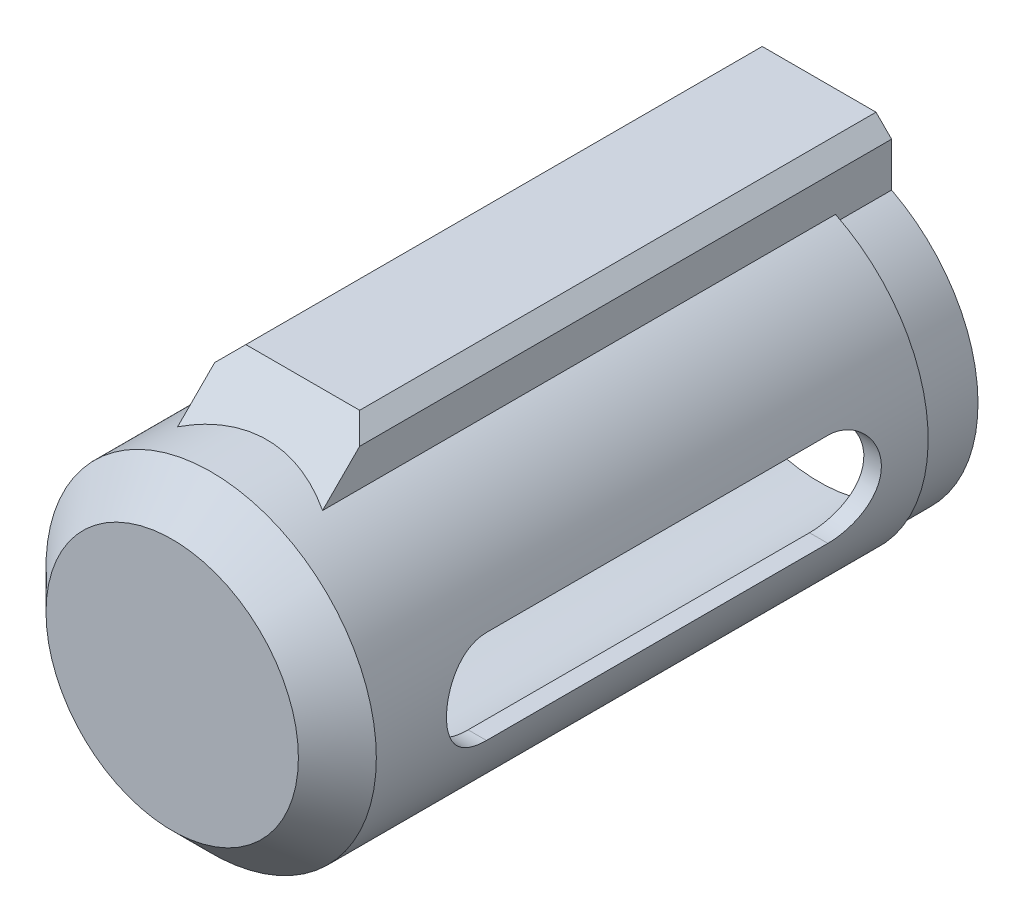
SolidWorks part; units mm, degrees
material "6061-T6 (SS)"
ref_plane "Front Plane" through (0, 0, 0) normal (0, 0, 1) x (1, 0, 0)
ref_plane "Top Plane" through (0, 0, 0) normal (0, 1, 0) x (1, 0, 0)
ref_plane "Right Plane" through (0, 0, 0) normal (1, 0, 0) x (0, 0, -1)
sketch "Sketch1" plane through (0, 0, 0) normal (0, 0, 1) x (1, 0, 0)
  line L0 (-7.5, 24) -> (-7.5, 17.3931)
  line L1 (-7.5, 24) -> (7.5, 24)
  line L2 (7.5, 24) -> (7.5, 17.3931)
  line L3 (9.3, 19.0415) -> (9.3, 25.8)
  line L4 (9.3, 25.8) -> (-9.3, 25.8)
  line L5 (-9.3, 25.8) -> (-9.3, 19.0415)
  circle A0 centre (0, 0) radius 18.4912 construction
  circle A1 centre (0, 0) radius 18.9412
  circle A2 centre (0, 0) radius 20.55 construction
  circle A3 centre (0, 0) radius 21.1912
  point P6 (7.5, 24)
  point P9 (7.3806, 24)
  point P11 (9.3, 25.8)
  point P12 (0, 0)
  point P13 (9.3, 25.6475)
  point P17 (-7.5, 24)
  point P19 (-7.3767, 24)
  point P21 (7.5, 24)
  point P23 (-9.3, 25.8)
  point P24 (-7.5, 24)
  point P25 (0, 0)
  point P26 (-7.2772, 17.4874)
  point P27 (-9.1561, 25.8)
  dimension "D1" = 36.9824
  dimension "D2" = 0.45
  dimension "D3" = 41.1
  dimension "D4" = 2.25
  dimension "D6" = 24
  dimension "D7" = 1.8
  dimension "D8" = 1.8
  dimension "D10" = 15
  dimension "D11" = 1.8
extrude "Boss-Extrude1" add sketch "Sketch1" along normal blind 65 contours A3 L2 A1 L0 | L0 L1 L2 A3 L3 L4 L5 region at (-7.6979, 21.9098, 0) region at (-8.0898, 18.6063, 0)
sketch "Sketch2" plane through (0, 0, 0) normal (0, 0, -1) x (-1, 0, 0)
  line L0 (-9.3, 19.0415) -> (-9.3, 18.1415)
  line L1 (9.3, 19.0415) -> (9.3, 18.1415)
  arc A0 (-9.3, 19.0415) -> (9.3, 19.0415) centre (0, 0) ccw
  arc A1 (-9.3, 19.0415) -> (9.3, 19.0415) centre (0, 0) ccw construction
  arc A2 (-9.3, 18.1415) -> (9.3, 18.1415) centre (0, 0) ccw
  point P10 (9.3493, 18.1161)
  dimension "D1" = 0.9
sketch "Sketch5" plane through (0, 0, 65) normal (0, 0, 1) x (1, 0, 0)
  line L1 (-9.3, 25.8) -> (-9.3, 17.3931)
  line L2 (-9.3, 17.3931) -> (-7.5, 17.3931)
  line L3 (9.3, 17.3931) -> (9.3, 25.8)
  line L4 (9.3, 19.0415) -> (9.3, 25.8) construction
  line L5 (9.3, 25.8) -> (-9.3, 25.8) construction
  line L6 (9.3, 25.8) -> (-9.3, 25.8)
  line L7 (-9.3, 25.8) -> (-9.3, 19.0415) construction
  line L8 (9.3, 17.3931) -> (7.5, 17.3931)
  arc A2 (-7.5, 17.3931) -> (7.5, 17.3931) centre (0, 0) cw
  arc A4 (-7.5, 17.3931) -> (7.5, 17.3931) centre (0, 0) ccw construction
  arc A5 (-9.3, 19.0415) -> (9.3, 19.0415) centre (0, 0) ccw construction
  arc A6 (-7.5, 17.3931) -> (7.5, 17.3931) centre (0, 0) ccw
  arc A7 (-9.3, 19.0415) -> (9.3, 19.0415) centre (0, 0) ccw
  line M3 (-9.3, 25.8) -> (-9.3, 19.0415)
  arc M4 (-9.3, 19.0415) -> (9.3, 19.0415) centre (0, 0) ccw
  line M5 (9.3, 19.0415) -> (9.3, 25.8)
  line M7 (9.3, 25.8) -> (-9.3, 25.8)
  line M9 (-7.5, 17.3931) -> (-7.5, 24)
  line M11 (-7.5, 24) -> (7.5, 24)
  line M13 (7.5, 24) -> (7.5, 17.3931)
  arc M14 (7.5, 17.3931) -> (-7.5, 17.3931) centre (0, 0) cw
extrude "Boss-Extrude3" add sketch "Sketch5" along normal blind 8 contours L3 L1 M14 M4 | L3 L1 M5 M7 M3 M9 M11 M13 | M9 M13 M11 region at (0, 25.5959, 65) region at (-9.8844, 18.2173, 65) region at (0, 21.1981, 65)
sketch "Sketch6" plane through (0, 0, 73) normal (0, 0, 1) x (1, 0, 0)
  circle A0 centre (0, 0) radius 21.1912
  circle A1 centre (0, 0) radius 18.9412
  circle A2 centre (0, 0) radius 18.9412 construction
extrude "Boss-Extrude4" add sketch "Sketch6" along normal blind 8
chamfer "Chamfer3" distance 6.75 angle 45 2 edges at (0, 25.8, 73) (0, 18.9412, 65)
sketch "Sketch7" plane through (0, 0, 81) normal (0, 0, 1) x (1, 0, 0)
  circle A1 centre (0, 0) radius 21.1912
  circle A2 centre (0, 0) radius 21.1912
  dimension "D1" = 0
extrude "Boss-Extrude5" add sketch "Sketch7" along normal blind 2
extrude "Cut-Extrude3" cut sketch "Sketch2" against normal blind 7.2
chamfer "Chamfer4" distance 5 angle 45 2 edges at (18.9412, 0, 81) (21.1912, 0, 83)
ref_plane "Plane1" through (-21.1912, 0, 0) normal (-1, 0, 0) x (0, 0, 1)
sketch "Sketch8" plane through (-21.1912, 0, 0) normal (-1, 0, 0) x (0, 0, 1)
  line L0 (7.2, 18.1415) -> (7.2, -20.3863) construction
  line L1 (19.2, -6) -> (63, -6)
  line L2 (19.2, -6) -> (19.2, 6)
  line L3 (19.2, 6) -> (63, 6)
  line L4 (63, -6) -> (63, 6)
  line L5 (41.1, 6) -> (41.1, -6) construction
  line L6 (19.2, 0) -> (63, 0) construction
  line L7 (78, -21.1912) -> (78, 21.1912) construction
  arc A0 (19.2, 6) -> (19.2, -6) centre (19.2, 0) ccw
  arc A1 (63, 6) -> (63, -6) centre (63, 0) cw
  point P0 (41.1, 0)
  point P10 (0, 0)
  dimension "D1" = 12
  dimension "D2" = 12
  dimension "D3" = 15
extrude "Cut-Extrude4" cut sketch "Sketch8" against normal through all contours L1 L4 L3 L2 | L2 A0 | A1 L4 region at (-21.1912, 0, 41.1) region at (-21.1912, 0, 16.6535) region at (-21.1912, 0, 65.5465)
chamfer "Chamfer5" distance 2 angle 45 4 edges at (-7.5, 24, 32.7733) (7.5, 24, 32.7733) (9.3, 25.8, 33.125) (-9.3, 25.8, 33.125)
